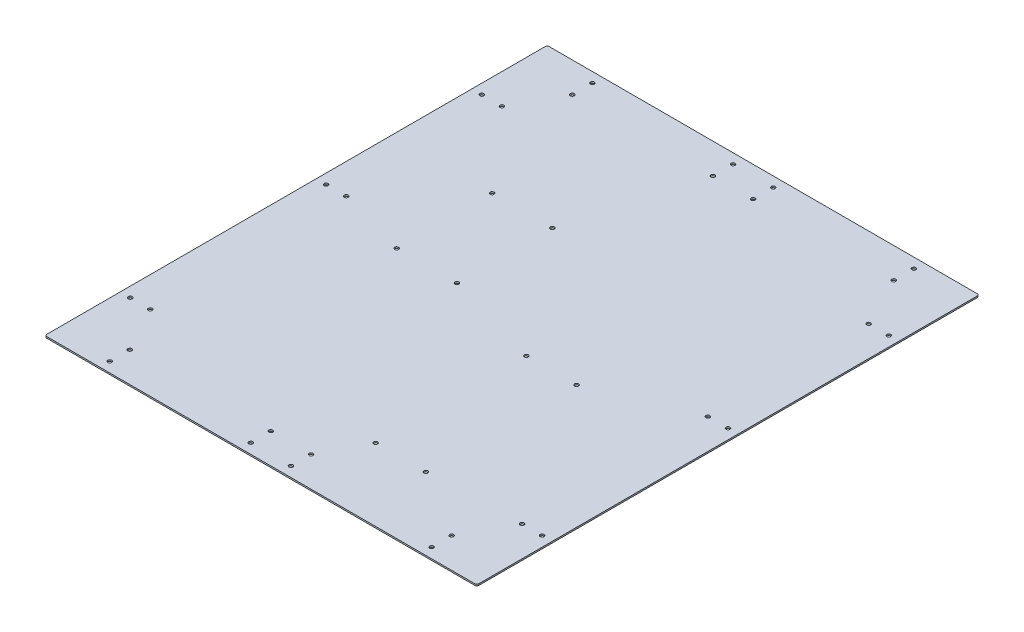
SolidWorks part; units mm, degrees
ref_plane "Front Plane" through (0, 0, 0) normal (0, 0, 1) x (1, 0, 0)
ref_plane "Top Plane" through (0, 0, 0) normal (0, 1, 0) x (1, 0, 0)
ref_plane "Right Plane" through (0, 0, 0) normal (1, 0, 0) x (0, 0, -1)
sketch "Sketch1" plane through (0, 0, 0) normal (0, 1, 0) x (1, 0, 0)
  line L1 (-215, -250) -> (215, -250)
  line L2 (-215, -250) -> (-215, 250)
  line L3 (-215, 250) -> (215, 250)
  line L4 (215, -250) -> (215, 250)
  line L5 (-215, -250) -> (215, 250) construction
  line L6 (-215, 250) -> (215, -250) construction
  point P0 (0, 0)
  dimension "D1" = 430
  dimension "D2" = 500
extrude "Boss-Extrude1" add sketch "Sketch1" along normal blind 1.5
sketch "Sketch6" plane through (0, 1.5, 0) normal (0, 1, 0) x (1, 0, 0)
  circle A0 centre (92.2927, -28) radius 1.95
  circle A1 centre (42.2927, -28) radius 1.95
  circle A2 centre (92.2927, -178) radius 1.95
  circle A3 centre (42.2927, -178) radius 1.95
  dimension "D1" = 50
  dimension "D2" = 150
sketch "Sketch7" plane through (0, 1.5, 0) normal (0, 1, 0) x (1, 0, 0)
  circle A0 centre (-114.98, 95.1924) radius 1.95
  circle A1 centre (-54.98, 95.1924) radius 1.95
  circle A2 centre (-54.98, 0.1924) radius 1.95
  circle A3 centre (-114.98, 0.1924) radius 1.95
  dimension "D1" = 95
  dimension "D2" = 60
sketch "Sketch12" plane through (0, 0, 0) normal (0, -1, 0) x (-1, 0, 0)
  line L0 (215, -250) -> (-215, -250) construction
  line L1 (-215, 250) -> (215, 250) construction
  line L2 (215, 250) -> (215, -250) construction
  line L3 (-215, -250) -> (-215, 250) construction
  circle A0 centre (-185, -175) radius 1.95
  circle A1 centre (-205, 170) radius 1.95
  circle A3 centre (-185, 10) radius 1.95
  circle A4 centre (-205, 10) radius 1.95
  circle A5 centre (-205, -175) radius 1.95
  circle A6 centre (-185, 170) radius 1.95
  circle A7 centre (205, -175) radius 1.95
  circle A8 centre (205, 20) radius 1.95
  circle A9 centre (185, 175) radius 1.95
  circle A10 centre (205, 175) radius 1.95
  circle A11 centre (185, -175) radius 1.95
  circle A12 centre (185, 20) radius 1.95
  circle A13 centre (160.3499, -240) radius 1.95
  circle A14 centre (160.3499, -220) radius 1.95
  circle A15 centre (20, -240) radius 1.95
  circle A16 centre (20, -220) radius 1.95
  circle A17 centre (-20, -220) radius 1.95
  circle A19 centre (-20, -240) radius 1.95
  circle A20 centre (-160, -240) radius 1.95
  circle A21 centre (-160, -220) radius 1.95
  circle A22 centre (160, 220) radius 1.95
  circle A23 centre (160, 240) radius 1.95
  circle A24 centre (20, 220) radius 1.95
  circle A25 centre (20, 240) radius 1.95
  circle A26 centre (-20, 220) radius 1.95
  circle A27 centre (-20, 240) radius 1.95
  circle A28 centre (-160, 220) radius 1.95
  circle A29 centre (-160, 240) radius 1.95
  dimension "D1" = 10
  dimension "D2" = 20
  dimension "D3" = 10
  dimension "D5" = 10
  dimension "D6" = 20
  dimension "D7" = 20
  dimension "D4" = 20
  dimension "D8" = 10
extrude "Cut-Extrude3" cut sketch "Sketch12" against normal blind 50.8
extrude "Cut-Extrude4" cut sketch "Sketch6" against normal blind 50.8
extrude "Cut-Extrude5" cut sketch "Sketch7" against normal blind 50.8
fillet "Fillet1" radius 2 4 edges at (215, 0.75, -250) (215, 0.75, 250) (-215, 0.75, 250) (-215, 0.75, -250)
sketch "Sketch13" plane through (0, 0, 0) normal (0, -1, 0) x (1, 0, 0)
  line L0 (114.139, 67.8293) -> (33.7223, 46.2817)
  line L1 (111.3737, 83.5389) -> (30.957, 61.9913)
  line L2 (111.3737, 83.5389) -> (112.1961, 80.4696)
  line L3 (112.1961, 80.4696) -> (31.7794, 58.922)
  line L4 (30.957, 61.9913) -> (31.7794, 58.922)
  line L5 (114.139, 67.8293) -> (114.9615, 64.76)
  line L6 (114.9615, 64.76) -> (34.5447, 43.2124)
  line L7 (33.7223, 46.2817) -> (34.5447, 43.2124)
  line L8 (97.051, 138.8211) -> (16.6342, 117.2735)
  line L9 (97.051, 138.8211) -> (97.8734, 135.7518)
  line L10 (97.8734, 135.7518) -> (17.4567, 114.2042)
  line L11 (16.6342, 117.2735) -> (17.4567, 114.2042)
  line L12 (105.9976, 100.9569) -> (25.5809, 79.4093)
  line L13 (105.9976, 100.9569) -> (106.8201, 97.8875)
  line L14 (106.8201, 97.8875) -> (26.4033, 76.3399)
  line L15 (25.5809, 79.4093) -> (26.4033, 76.3399)
  line L16 (101.6201, 121.1327) -> (21.2034, 99.5851)
  line L17 (101.6201, 121.1327) -> (102.4426, 118.0633)
  line L18 (102.4426, 118.0633) -> (22.0258, 96.5157)
  line L19 (21.2034, 99.5851) -> (22.0258, 96.5157)
  line L20 (93.1191, 158.1022) -> (12.7023, 136.5546)
  line L21 (93.1191, 158.1022) -> (93.9415, 155.0329)
  line L22 (93.9415, 155.0329) -> (13.5248, 133.4853)
  line L23 (12.7023, 136.5546) -> (13.5248, 133.4853)
